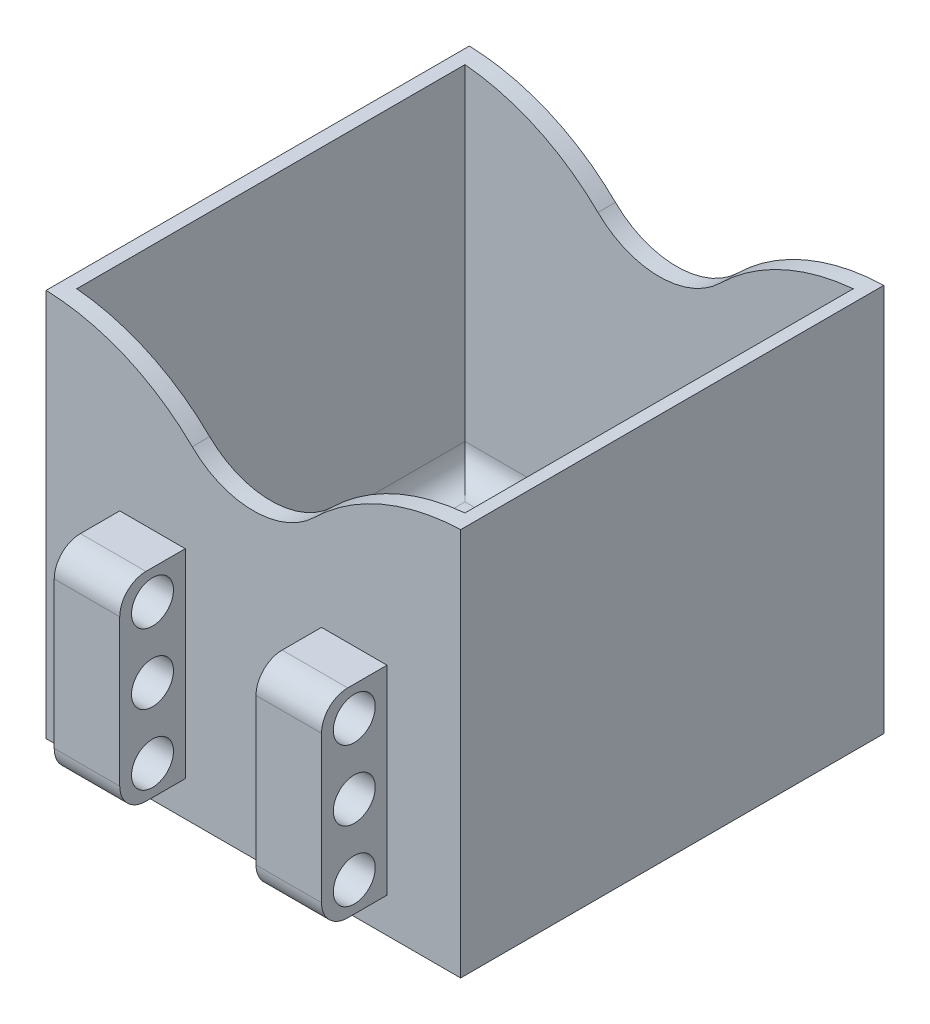
SolidWorks part; units mm, degrees
ref_plane "Front Plane" through (0, 0, 0) normal (0, 0, 1) x (1, 0, 0)
ref_plane "Top Plane" through (0, 0, 0) normal (0, 1, 0) x (1, 0, 0)
ref_plane "Right Plane" through (0, 0, 0) normal (1, 0, 0) x (0, 0, -1)
sketch "Sketch1" plane through (0, 0, 0) normal (0, 1, 0) x (1, 0, 0)
  line L1 (-31.9422, 29.4379) -> (15.5078, 29.4379)
  line L2 (-31.9422, 29.4379) -> (-31.9422, -19.0121)
  line L3 (-31.9422, -19.0121) -> (15.5078, -19.0121)
  line L4 (15.5078, 29.4379) -> (15.5078, -19.0121)
  dimension "D1" = 47.45
  dimension "D2" = 48.45
extrude "Boss-Extrude1" add sketch "Sketch1" along normal blind 44.45
sketch "Sketch2" plane through (0, 44.45, 0) normal (0, 1, 0) x (1, 0, 0)
  line L0 (-31.9422, 5.2129) -> (15.5078, 5.2129) construction
  line L1 (-31.9422, 29.4379) -> (-31.9422, -19.0121) construction
  line L2 (15.5078, -19.0121) -> (15.5078, 29.4379) construction
  line L4 (14.0078, -17.0121) -> (-30.4422, -17.0121)
  line L5 (14.0078, -17.0121) -> (14.0078, 27.4379)
  line L6 (14.0078, 27.4379) -> (-30.4422, 27.4379)
  line L7 (-30.4422, -17.0121) -> (-30.4422, 27.4379)
  line L8 (14.0078, -17.0121) -> (-30.4422, 27.4379) construction
  line L9 (14.0078, 27.4379) -> (-30.4422, -17.0121) construction
  point P6 (-8.2172, 5.2129)
  dimension "D1" = 44.45
  dimension "D2" = 44.45
extrude "Cut-Extrude1" cut sketch "Sketch2" against normal blind 40.45
sketch "Sketch3" plane through (0, 0, 19.0121) normal (0, 0, 1) x (1, 0, 0)
  line L0 (-8.2172, 44.45) -> (-8.2172, 0) construction
  line L1 (-23.5172, 26.8) -> (-16.0172, 26.8)
  line L2 (-23.5172, 26.8) -> (-23.5172, 4)
  line L3 (-23.5172, 4) -> (-16.0172, 4)
  line L4 (-16.0172, 26.8) -> (-16.0172, 4)
  line L5 (-23.5172, 26.8) -> (-16.0172, 4) construction
  line L6 (-23.5172, 4) -> (-16.0172, 26.8) construction
  line L7 (-31.9422, 44.45) -> (15.5078, 44.45) construction
  line L8 (-31.9422, 0) -> (15.5078, 0) construction
  line L10 (-0.4172, 26.8) -> (7.0828, 26.8)
  line L11 (-0.4172, 26.8) -> (-0.4172, 4)
  line L12 (-0.4172, 4) -> (7.0828, 4)
  line L13 (7.0828, 26.8) -> (7.0828, 4)
  line L14 (-0.4172, 26.8) -> (7.0828, 4) construction
  line L15 (-0.4172, 4) -> (7.0828, 26.8) construction
  point P0 (-19.7672, 15.4)
  point P12 (3.3328, 15.4)
  dimension "D1" = 7.5
  dimension "D2" = 22.8
  dimension "D3" = 7.8
  dimension "D4" = 4
  dimension "D5" = 22.8
  dimension "D6" = 7.5
  dimension "D7" = 4
  dimension "D8" = 7.8
extrude "Boss-Extrude2" add sketch "Sketch3" along normal blind 7.5
sketch "Sketch4" plane through (7.0828, 0, 0) normal (1, 0, 0) x (0, 0, -1)
  line L0 (-22.7621, 26.8) -> (-22.7621, 4) construction
  line L1 (-26.5121, 26.8) -> (-19.0121, 26.8) construction
  line L2 (-26.5121, 4) -> (-19.0121, 4) construction
  circle A0 centre (-22.7621, 23.4) radius 2.4
  circle A1 centre (-22.7621, 7.4) radius 2.4
  circle A2 centre (-22.7621, 15.4) radius 2.4
  dimension "D1" = 3.4
  dimension "D2" = 3.4
extrude "Cut-Extrude2" cut sketch "Sketch4" against normal through all
fillet "Fillet1" radius 3 4 edges at (-19.7672, 26.8, 26.5121) (-19.7672, 4, 26.5121) (3.3328, 4, 26.5121) (3.3328, 26.8, 26.5121)
sketch "Sketch5" plane through (-31.9422, 0, 0) normal (-1, 0, 0) x (0, 0, 1)
  line L0 (-5.2129, 44.45) -> (-5.2129, 0) construction
  line L1 (-29.4379, 44.45) -> (19.0121, 44.45) construction
  line L2 (-29.4379, 0) -> (19.0121, 0) construction
  line L4 (-0.7735, 0) -> (-9.6523, 0)
  line L5 (-0.7735, 0) -> (-0.7735, 5)
  line L6 (-0.7735, 5) -> (-9.6523, 5)
  line L7 (-9.6523, 0) -> (-9.6523, 5)
  line L8 (-0.7735, 0) -> (-9.6523, 5) construction
  line L9 (-0.7735, 5) -> (-9.6523, 0) construction
  point P6 (-5.2129, 2.5)
  point P13 (19.0121, 0)
  dimension "D1" = 5
  dimension "D2" = 8.8788
  dimension "D3" = 0
extrude "Boss-Extrude3" add sketch "Sketch5" along normal blind 10
fillet "Fillet2" radius 10 1 edges at (-31.9422, 5, -5.2129)
fillet "Fillet3" radius 2 1 edges at (-41.9422, 5, -5.2129)
fillet "Fillet4" radius 2 2 edges
fillet "Fillet5" radius 3 4 edges at (-8.2172, 4, -27.4379) (14.0078, 4, -5.2129) (-8.2172, 4, 17.0121) (-30.4422, 4, -5.2129)
sketch "Sketch6" plane through (0, 4, 0) normal (0, 1, 0) x (1, 0, 0)
  line L0 (-8.2172, 24.4379) -> (-8.2172, -14.0121) construction
  line L1 (11.0078, 24.4379) -> (-27.4422, 24.4379) construction
  line L2 (-27.4422, -14.0121) -> (11.0078, -14.0121) construction
  circle A0 centre (-8.2172, 5.2129) radius 10
extrude "Cut-Extrude3" cut sketch "Sketch6" against normal blind 10
sketch "Sketch7" plane through (0, 0, -29.4379) normal (0, 0, -1) x (-1, 0, 0)
  line L0 (-15.5078, 44.45) -> (31.9422, 44.45) construction
  arc A0 (18.2172, 44.45) -> (-1.7828, 44.45) centre (8.2172, 44.45) cw
  dimension "D1" = 10
extrude "Cut-Extrude5" cut sketch "Sketch7" against normal through all and the other way through all flip side to cut
fillet "Fillet6" radius 25 4 edges at (1.7828, 44.45, 18.0121) (-18.2172, 44.45, 18.0121) (-18.2172, 44.45, -28.4379) (1.7828, 44.45, -28.4379)
